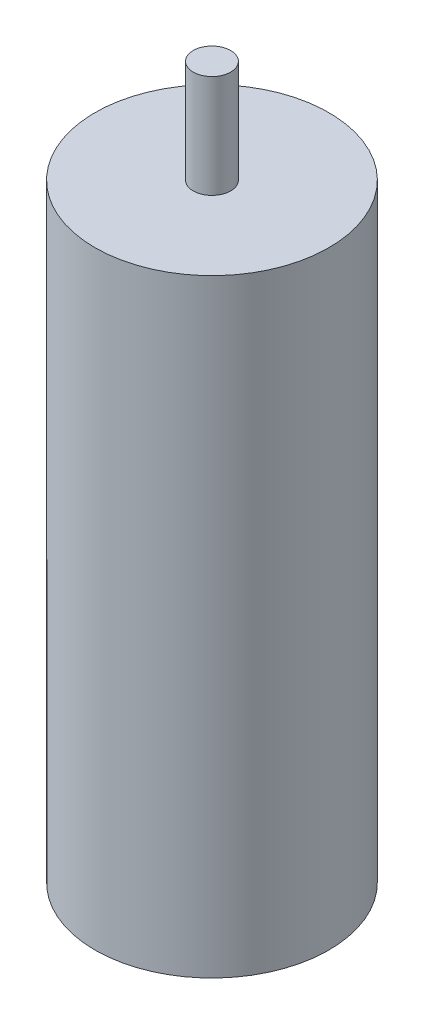
SolidWorks part; units mm, degrees
material "1023 Carbon Steel Sheet (SS)"
ref_plane "Front Plane" through (0, 0, 0) normal (0, 0, 1) x (1, 0, 0)
ref_plane "Top Plane" through (0, 0, 0) normal (0, 1, 0) x (1, 0, 0)
ref_plane "Right Plane" through (0, 0, 0) normal (1, 0, 0) x (0, 0, -1)
sketch "Sketch1" plane through (0, 0, 0) normal (0, 1, 0) x (1, 0, 0)
  circle A0 centre (0, 0) radius 12.5
  dimension "D1" = 25
extrude "Boss-Extrude1" add sketch "Sketch1" along normal blind 65
sketch "Sketch3" plane through (0, 65, 0) normal (0, 1, 0) x (1, 0, 0)
  circle A0 centre (0, 0) radius 2
  dimension "D1" = 4
extrude "Boss-Extrude2" add sketch "Sketch3" along normal blind 11
